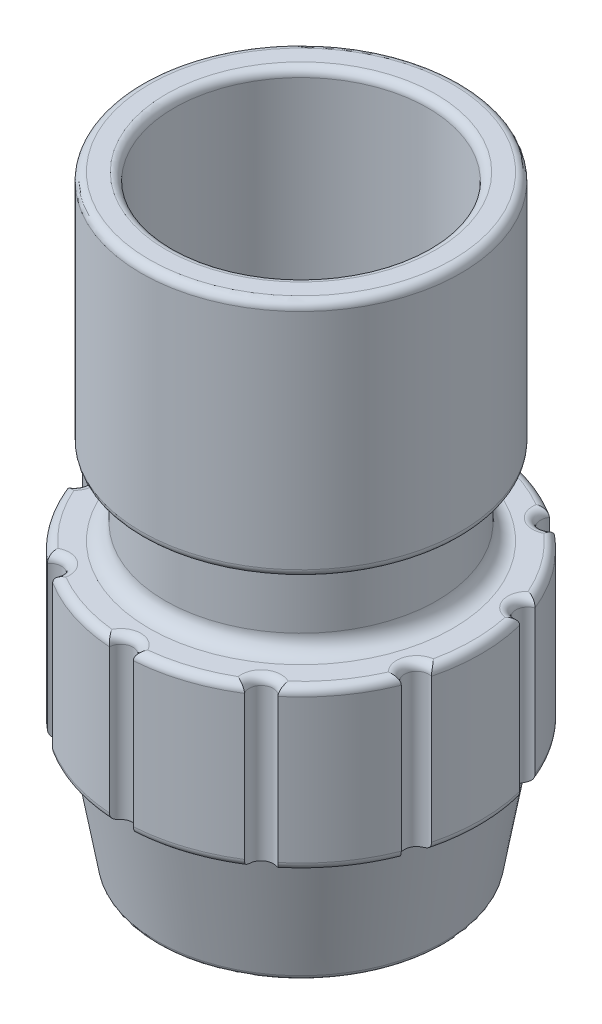
SolidWorks part; units mm, degrees
material "PE Высокой плотности"
ref_plane "Front" through (0, 0, 0) normal (0, 0, 1) x (1, 0, 0)
ref_plane "Top" through (0, 0, 0) normal (0, 1, 0) x (1, 0, 0)
ref_plane "Right" through (0, 0, 0) normal (1, 0, 0) x (0, 0, -1)
sketch "Эскиз1" plane through (0, 0, 0) normal (0, 1, 0) x (1, 0, 0)
  circle A0 centre (0, 0) radius 16
  dimension "D1" = 32
extrude "Вытянуть-Тонкостенный1" add sketch "Эскиз1" along normal blind 15 draft 10 thin draft outward yes thin type one direction wall 1.9
sketch "Эскиз2" plane through (0, 15, 0) normal (0, 1, 0) x (1, 0, 0)
  circle A2 centre (0, 0) radius 22.5449
  circle A3 centre (0, 0) radius 22.5449
  dimension "D1" = 2
extrude "Бобышка-Вытянуть1" add sketch "Эскиз2" along normal blind 20
fillet "Скругление1" radius 0.7 2 edges at (0, 0, 16) (17.9, 0, 0)
fillet "Скругление2" radius 1 1 edges at (0, 15, 22.5449)
sketch "Эскиз3" plane through (0, 35, 0) normal (0, 1, 0) x (1, 0, 0)
  line L0 (0, 0) -> (0, 22.5449) construction
  circle A0 centre (0, 22.5449) radius 1.5
  dimension "D1" = 3
extrude "Вырез-Вытянуть1" cut sketch "Эскиз3" against normal through all
sketch3d "Трехмерный эскиз1"
  line L0 (0, 35, 0) -> (0, 0, 0) construction
ref_axis "Ось1" through (0, 35, 0) along (0, -1, 0)
pattern_circular "Круговой массив1" count 10 over 360 about axis through (0, 35, 0) along (0, -1, 0) of "Вырез-Вытянуть1"
sketch "Эскиз4" plane through (0, 35, 0) normal (0, 1, 0) x (1, 0, 0)
  circle A0 centre (0, 0) radius 17
  dimension "D1" = 34
extrude "Бобышка-Вытянуть2" add sketch "Эскиз4" along normal blind 10
fillet "Скругление3" radius 2 1 edges at (0, 35, 17)
sketch "Эскиз5" plane through (0, 45, 0) normal (0, 1, 0) x (1, 0, 0)
  circle A1 centre (0, 0) radius 20
  dimension "D1" = 40
extrude "Бобышка-Вытянуть3" add sketch "Эскиз5" along normal blind 30
sketch "Эскиз6" plane through (0, 75, 0) normal (0, 1, 0) x (1, 0, 0)
  circle A0 centre (0, 0) radius 15.885
  dimension "D1" = 31.77
extrude "Вырез-Вытянуть2" cut sketch "Эскиз6" against normal through all
fillet "Скругление4" radius 1 1 edges at (0, 45, 20)
fillet "Скругление5" radius 1 2 edges at (0, 75, 20) (0, 75, 15.885)
fillet "Скругление6" radius 1 20 edges at (-6.9668, 35, -21.4415) (0, 35, -21.0449) (6.9668, 35, -21.4415) (12.3699, 35, -17.0257) (18.2392, 35, -13.2516) (20.0149, 35, -6.5032) (22.5449, 35, 0) (20.0149, 35, 6.5032) (18.2392, 35, 13.2516) (12.3699, 35, 17.0257) (6.9668, 35, 21.4415) (0, 35, 21.0449) (-6.9668, 35, 21.4415) (-12.3699, 35, 17.0257) (-18.2392, 35, 13.2516) (-20.0149, 35, 6.5032) (-22.5449, 35, 0) (-20.0149, 35, -6.5032) (-18.2392, 35, -13.2516) (-12.3699, 35, -17.0257)
